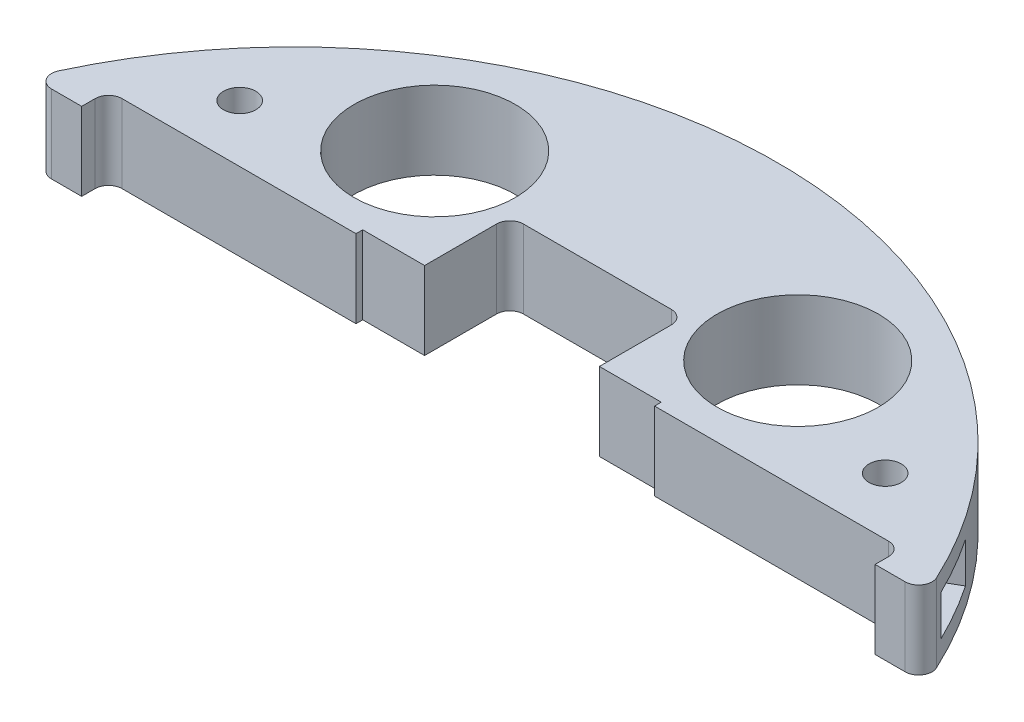
SolidWorks part; units mm, degrees
material "ABS"
ref_plane "Front Plane" through (0, 0, 0) normal (0, 0, 1) x (1, 0, 0)
ref_plane "Top Plane" through (0, 0, 0) normal (0, 1, 0) x (1, 0, 0)
ref_plane "Right Plane" through (0, 0, 0) normal (1, 0, 0) x (0, 0, -1)
sketch "Sketch1" plane through (0, 0, 0) normal (0, 1, 0) x (1, 0, 0)
  line L0 (0, -85) -> (-32.2211, -64.3879) construction
  line L1 (0, -85) -> (0, 0) construction
  arc A0 (36.2245, -62.2237) -> (-36.2245, -62.2237) centre (0, 0) ccw
  arc A1 (29.8119, -61.0352) -> (-29.8119, -61.0352) centre (0, -85) ccw
  arc A2 (36.2245, -62.2237) -> (29.8119, -61.0352) centre (33.7089, -57.9026) cw
  arc A3 (-29.8119, -61.0352) -> (-36.2245, -62.2237) centre (-33.7089, -57.9026) cw
  dimension "D1" = 144
  dimension "D2" = 76.5
  dimension "D4" = 5
  dimension "D3" = 85
extrude "Boss-Extrude1" add sketch "Sketch1" along normal mid plane 11.6
sketch "solenoid placement" plane through (0, 5.8, 0) normal (0, 1, 0) x (1, 0, 0)
  line L0 (0, 0) -> (0, -36) construction
  line L5 (-19, -36) -> (19, -36)
  line L7 (19, -36) -> (19, 28)
  line L9 (19, 28) -> (-19, 28)
  line L11 (-19, 28) -> (-19, -36)
  circle A1 centre (0, 0) radius 72 construction
  arc A2 (36.2245, -62.2237) -> (-36.2245, -62.2237) centre (0, 0) ccw construction
  dimension "D1" = 36
  dimension "D2" = 64
  dimension "D3" = 38
extrude "Cut-Extrude1" cut sketch "solenoid placement" against normal through all
sketch "Sketch4" plane through (0, 5.8, 0) normal (0, 1, 0) x (1, 0, 0)
  line L1 (-13, 28) -> (13, 28)
  line L2 (-13, 28) -> (-13, 43.2)
  line L4 (13, 28) -> (13, 43.2)
  line L5 (11, 45.2) -> (-11, 45.2)
  line L6 (19, 28) -> (-19, 28) construction
  arc A0 (11, 45.2) -> (13, 43.2) centre (11, 43.2) cw
  arc A1 (-11, 45.2) -> (-13, 43.2) centre (-11, 43.2) ccw
  point P6 (0, 28)
  dimension "D1" = 2
  dimension "D2" = 26
  dimension "D3" = 17.2
extrude "Cut-Extrude4" cut sketch "Sketch4" against normal through all
sketch "Sketch5" plane through (0, 5.8, 0) normal (0, 1, 0) x (1, 0, 0)
  line L0 (0, 0) -> (0, 72) construction
  arc A0 (36.2245, -62.2237) -> (-36.2245, -62.2237) centre (0, 0) ccw construction
  circle A1 centre (27, 48) radius 12
  circle A3 centre (-27, 48) radius 12
  dimension "D3" = 24
  dimension "D1" = 27
  dimension "D2" = 48
extrude "Cut-Extrude5" cut sketch "Sketch5" against normal through all
sketch "Sketch6" plane through (0, 5.8, 0) normal (0, 1, 0) x (1, 0, 0)
  line L0 (0, 0) -> (0, 72) construction
  arc A0 (36.2245, -62.2237) -> (-36.2245, -62.2237) centre (0, 0) ccw construction
  circle A1 centre (48, 40) radius 2.4
  circle A6 centre (-48, 40) radius 2.4
  dimension "D3" = 4.8
  dimension "D1" = 48
  dimension "D2" = 40
extrude "Cut-Extrude6" cut sketch "Sketch6" against normal through all
sketch "Sketch3" plane through (0, 5.8, 0) normal (0, 1, 0) x (1, 0, 0)
  line L0 (-19, 28) -> (19, 28)
  line L1 (-72, -31.5) -> (72, -31.5) construction
  line L2 (-72, -31.5) -> (-72, 27.5)
  line L3 (-59, 31.5) -> (-19, 31.5)
  line L4 (72, -31.5) -> (72, 27.5)
  line L5 (0, -31.5) -> (0, 31.5) construction
  line L6 (72, 27.5) -> (59, 27.5)
  line L7 (19, 28) -> (19, 31.5)
  line L8 (-19, 28) -> (-19, 31.5)
  line L9 (19, 31.5) -> (59, 31.5)
  line L10 (-72, -31.5) -> (-72, -101.6464)
  line L11 (72, -31.5) -> (72, -101.6464)
  line L12 (72, -101.6464) -> (-72, -101.6464)
  line L13 (59, 27.5) -> (59, 31.5)
  line L14 (-59, 27.5) -> (-59, 31.5)
  line L15 (-72, 27.5) -> (-59, 27.5)
  arc A0 (36.2245, -62.2237) -> (-36.2245, -62.2237) centre (0, 0) ccw construction
  point P0 (0, 0)
  dimension "D2" = 13
  dimension "D1" = 63
  dimension "D3" = 4
extrude "Cut-Extrude3" cut sketch "Sketch3" against normal through all
sketch "Sketch7" plane through (0, 0, 0) normal (0, 1, 0) x (1, 0, 0)
  line L0 (0, 0) -> (62.3538, 36) construction
  line L1 (0, 0) -> (-62.3538, 36) construction
  line L2 (0, 0) -> (0, 72) construction
  arc A0 (0, 72) -> (62.3538, 36) centre (0, 0) cw construction
  arc A1 (0, 72) -> (-62.3538, 36) centre (0, 0) ccw construction
  arc A2 (66.5413, 27.5) -> (-66.5413, 27.5) centre (0, 0) ccw construction
  dimension "D1" = 120
fillet "Fillet1" radius 2 4 edges at (-66.5413, 0, -27.5) (-59, 0, -31.5) (59, 0, -31.5) (66.5413, 0, -27.5)
sketch "Sketch8" plane through (0, 0, 0) normal (0, 1, 0) x (1, 0, 0)
  line L0 (5, 71.8262) -> (5, 68.9262)
  line L1 (0, 0) -> (64.7033, 31.583) construction
  line L2 (64.7033, 31.583) -> (59.7033, 40.2432) construction
  line L3 (64.7033, 31.583) -> (62.1918, 30.133)
  line L4 (62.1918, 30.133) -> (57.1918, 38.7932)
  line L5 (59.7033, 40.2432) -> (57.1918, 38.7932)
  line L6 (0, 0) -> (59.7033, 40.2432) construction
  line L7 (5, 68.9262) -> (-5, 68.9262)
  line L8 (-5, 71.8262) -> (-5, 68.9262)
  line L9 (5, 71.8262) -> (-5, 71.8262) construction
  line L10 (-59.7033, 40.2432) -> (-57.1918, 38.7932)
  line L11 (-57.1918, 38.7932) -> (-62.1918, 30.133)
  line L12 (-64.7033, 31.583) -> (-62.1918, 30.133)
  line L13 (-59.7033, 40.2432) -> (-64.7033, 31.583) construction
  arc A0 (59.7033, 40.2432) -> (64.7033, 31.583) centre (0, 0) cw
  arc A2 (-5, 71.8262) -> (5, 71.8262) centre (0, 0) cw
  arc A3 (-64.7033, 31.583) -> (-59.7033, 40.2432) centre (0, 0) cw
  point P4 (62.3538, 36)
  point P10 (-62.3538, 36)
  point P18 (0, 0)
  dimension "D1" = 10
  dimension "D2" = 2.9
extrude "Cut-Extrude7" cut sketch "Sketch8" against normal mid plane 6
sketch "Sketch9" plane through (0, 5.8, 0) normal (0, 1, 0) x (1, 0, 0)
  line L1 (22.2, -32.5) -> (-22.2, -32.5)
  line L2 (22.2, -32.5) -> (22.2, 32.5)
  line L3 (22.2, 32.5) -> (-22.2, 32.5)
  line L4 (-22.2, -32.5) -> (-22.2, 32.5)
  line L5 (22.2, -32.5) -> (-22.2, 32.5) construction
  line L6 (22.2, 32.5) -> (-22.2, -32.5) construction
  point P0 (0, 0)
  dimension "D1" = 44.4
  dimension "D2" = 65
extrude "Cut-Extrude8" cut sketch "Sketch9" against normal through all
equation "\"smallPulleyTeeth\"= 15"
equation "\"largePulleyTeeth\"= 30"
equation "\"eighthThick\"= 2.9mm"
equation "\"sixteenthThick\" = 1.7mm"
equation "\"quarterThick\"=6.0mm"
equation "\"OD\" = 145mm"
equation "\"puckAngle\" = 60.5deg"
equation "\"puckDiam\" = 76.5mm"
equation "\"D2@Sketch1\"=\"puckDiam\""
equation "\"D1@Boss-Extrude1\"=\"eighthThick\"*4"
equation "\"axlePress\" = 5.9mm"
equation "\"press\" = 0.2mm"
equation "\"wheelClear\" = 0.3mm"
equation "\"10-32clear\" = 4.8mm"
equation "\"6-32clear\" = 3.3mm"
equation "\"8-32clear\" = 4.0mm"
equation "\"wheelHeight\" = 22mm"
equation "\"wheelWell\" = 65mm"
equation "\"puckDist\" = 85mm"
equation "\"scoopFillet\" = 5mm"
equation "\"4-40clear\" = 3.0mm"
equation "\"D3@Sketch1\"=\"puckDist\""
equation "\"D4@Sketch1\"=\"scoopFillet\""
equation "\"D3@Sketch6\"=\"10-32clear\""
equation "\"D2@Sketch8\"=\"eighthThick\""
equation "\"D2@Sketch9\"=\"wheelWell\""
